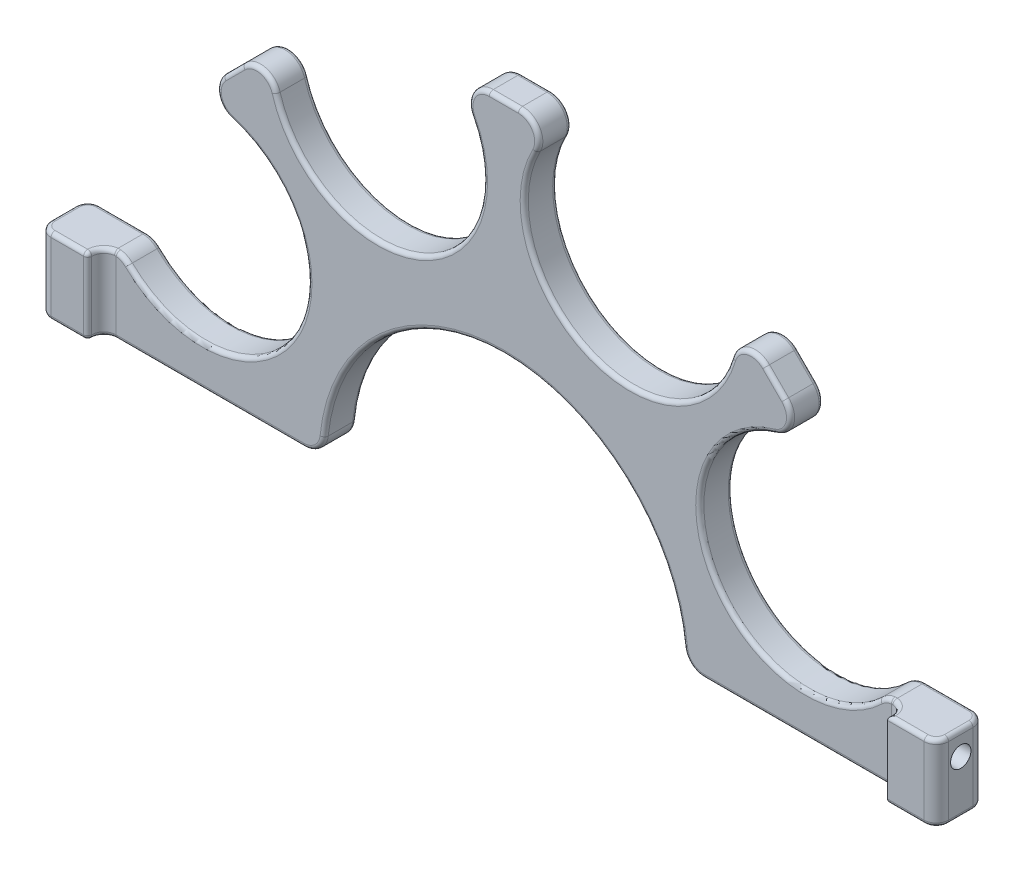
SolidWorks part; units mm, degrees
ref_plane "Front Plane" through (0, 0, 0) normal (0, 0, 1) x (1, 0, 0)
ref_plane "Top Plane" through (0, 0, 0) normal (0, 1, 0) x (1, 0, 0)
ref_plane "Right Plane" through (0, 0, 0) normal (1, 0, 0) x (0, 0, -1)
sketch "Sketch2" plane through (0, 0, 0) normal (0, 0, 1) x (1, 0, 0)
  line L0 (-74.1335, -21.5668) -> (-31, 21.5668) construction
  line L1 (-110.25, -57.5) -> (110.25, -57.5) construction
  line L2 (-110.25, -57.5) -> (-110.25, 57.5) construction
  line L3 (-110.25, 57.5) -> (110.25, 57.5) construction
  line L4 (110.25, -57.5) -> (110.25, 57.5) construction
  line L5 (-110.25, -57.5) -> (110.25, 57.5) construction
  line L6 (-110.25, 57.5) -> (110.25, -57.5) construction
  line L7 (-31, 21.5668) -> (31, 21.5668) construction
  line L8 (31, 21.5668) -> (74.1335, -21.5668) construction
  line L9 (0, 21.5668) -> (0, -21.5668) construction
  circle A0 centre (-74.1335, -21.5668) radius 27
  circle A1 centre (-31, 21.5668) radius 27
  circle A2 centre (31, 21.5668) radius 27
  circle A3 centre (74.1335, -21.5668) radius 27
  point P0 (0, 0)
  point P14 (0, 21.5668)
  point P24 (0, 0)
  dimension "D1" = 54
  dimension "D2" = 8
  dimension "D3" = 7
  dimension "D4" = 115
  dimension "D5" = 220.5
  dimension "D7" = 135
sketch "Sketch3" plane through (0, 0, 0) normal (0, 0, 1) x (1, 0, 0)
  line L0 (-13.7572, 41.0266) -> (13.7572, 41.0266)
  line L1 (-76.3601, 4.3377) -> (-56.9045, 23.7933)
  line L2 (76.3601, 4.3377) -> (56.9045, 23.7933)
  line L3 (31, 21.5668) -> (74.1335, -21.5668) construction
  line L4 (-74.1335, -21.5668) -> (-31, 21.5668) construction
  line L5 (-55.1453, 11.923) -> (-6.8547, 31.2105) construction
  line L6 (-55.1453, 11.923) -> (-56.9045, 23.7933) construction
  line L7 (-6.8547, 31.2105) -> (-13.7572, 41.0266) construction
  line L8 (-93.5934, -38.8096) -> (-110.25, -38.8096)
  line L9 (-110.25, -57.5) -> (-110.25, 57.5) construction
  line L10 (-110.25, -38.8096) -> (-110.25, -57.5)
  line L11 (-110.25, -57.5) -> (-44.3831, -57.5)
  line L12 (110.25, -57.5) -> (110.25, -38.8096)
  line L13 (110.25, -57.5) -> (110.25, 57.5) construction
  line L14 (110.25, -38.8096) -> (93.5934, -38.8096)
  line L15 (-64.4897, 2.5786) -> (-83.7773, -45.7121) construction
  line L16 (-64.4897, 2.5786) -> (-76.3601, 4.3377) construction
  line L17 (-83.7773, -45.7121) -> (-93.5934, -38.8096) construction
  line L18 (-110.25, -57.5) -> (110.25, -57.5) construction
  line L19 (-44.3831, -57.5) -> (44.3831, -57.5) construction
  line L20 (44.3831, -57.5) -> (110.25, -57.5)
  arc A0 (-93.5934, -38.8096) -> (-76.3601, 4.3377) centre (-74.1335, -21.5668) ccw
  arc A1 (-56.9045, 23.7933) -> (-13.7572, 41.0266) centre (-31, 21.5668) ccw
  arc A3 (13.7572, 41.0266) -> (56.9045, 23.7933) centre (31, 21.5668) ccw
  arc A4 (76.3601, 4.3377) -> (93.5934, -38.8096) centre (74.1335, -21.5668) ccw
  circle A5 centre (-31, 21.5668) radius 27 construction
  arc A6 (-76.3601, 4.3377) -> (-93.5934, -38.8096) centre (-74.1335, -21.5668) ccw construction
  arc A7 (-13.7572, 41.0266) -> (-56.9045, 23.7933) centre (-31, 21.5668) ccw construction
  arc A8 (56.9045, 23.7933) -> (13.7572, 41.0266) centre (31, 21.5668) ccw construction
  arc A9 (93.5934, -38.8096) -> (76.3601, 4.3377) centre (74.1335, -21.5668) ccw construction
  arc A10 (-44.3831, -57.5) -> (44.3831, -57.5) centre (0, -57.5) cw
  point P11 (0, -13.1169)
  dimension "D1" = 1
  dimension "D2" = 12
  dimension "D3" = 12
extrude "Boss-Extrude1" add sketch "Sketch3" along normal mid plane 8
sketch "Sketch4" plane through (0, 0, 4) normal (0, 0, 1) x (1, 0, 0)
  line L0 (-110.25, -57.5) -> (-44.3831, -57.5) construction
  line L1 (-110.25, -38.8096) -> (-98.25, -38.8096)
  line L2 (-110.25, -38.8096) -> (-110.25, -57.5)
  line L3 (-110.25, -57.5) -> (-98.25, -57.5)
  line L4 (-98.25, -38.8096) -> (-98.25, -57.5)
  dimension "D1" = 12
extrude "Boss-Extrude2" add sketch "Sketch4" along normal blind 4
sketch "Sketch5" plane through (0, -57.5, 0) normal (0, -1, 0) x (-1, 0, 0)
  line L0 (98.25, -8) -> (110.25, 4) construction
  circle A0 centre (104.25, -2) radius 2.5
  dimension "D1" = 5
extrude "Cut-Extrude1" cut sketch "Sketch5" against normal blind 8
sketch "Sketch6" plane through (-110.25, 0, 0) normal (-1, 0, 0) x (0, 0, 1)
  line L0 (8, -38.8096) -> (-4, -38.8096) construction
  line L1 (8, -57.5) -> (-4, -57.5) construction
  circle A0 centre (2, -44.5) radius 2.5
  point P4 (2, -38.8096)
  dimension "D1" = 5
  dimension "D2" = 13
extrude "Cut-Extrude2" cut sketch "Sketch6" against normal blind 10
mirror "Mirror1" about plane through (0, 0, 0) normal (1, 0, 0) of "Cut-Extrude2", "Cut-Extrude1", "Boss-Extrude2"
fillet "Fillet2" radius 5 10 edges at (44.3831, -57.5, 0) (93.5934, -38.8096, 0) (76.3601, 4.3377, 0) (56.9045, 23.7933, 0) (13.7572, 41.0266, 0) (-13.7572, 41.0266, 0) (-76.3601, 4.3377, 0) (-93.5934, -38.8096, 0) (-44.3831, -57.5, 0) (-56.9045, 23.7933, 0)
fillet "Fillet3" radius 3 6 edges at (-110.25, -48.1548, -4) (-110.25, -48.1548, 8) (110.25, -48.1548, 8) (110.25, -48.1548, -4) (98.25, -48.1548, 4) (-98.25, -48.1548, 4)
fillet "Fillet4" radius 1 67 edges at (-102.75, -57.5, 8) (102.75, -57.5, 8) (109.3713, -57.5, 7.1213) (110.25, -57.5, 2) (109.3713, -57.5, -3.1213) (78.1897, -57.5, -4) (45.7776, -56.2102, -4) (0, -13.1169, -4) (-45.7776, -56.2102, -4) (-78.1897, -57.5, -4) (-109.3713, -57.5, -3.1213) (-110.25, -57.5, 2) (98.25, -57.5, 7.5) (97.3713, -57.5, 4.8787) (72.1897, -57.5, 4) (45.7776, -56.2102, 4) (0, -13.1169, 4) (-45.7776, -56.2102, 4) (-72.1897, -57.5, 4) (98.25, -38.8096, 7.5) (97.5336, -38.8096, 5.0544) (93.6285, -39.271, 4) (51.667, -34.6533, 4) (70.2819, 6.9491, 4) (66.6323, 14.0655, 4) (59.5158, 17.7152, 4) (21.2405, -2.532, 4) (7.8604, 38.6091, 4) (0, 41.0266, 4) (-7.8604, 38.6091, 4) (-21.2405, -2.532, 4) (-59.5158, 17.7152, 4) (-66.6323, 14.0655, 4) (-70.2819, 6.9491, 4) (-51.667, -34.6533, 4) (-93.6285, -39.271, 4) (102.75, -38.8096, 8) (109.3713, -38.8096, 7.1213) (110.25, -38.8096, 2) (109.3713, -38.8096, -3.1213) (101.4883, -38.8096, -4) (93.8474, -39.1761, -4) (51.667, -34.6533, -4) (70.2819, 6.9491, -4) (66.6323, 14.0655, -4) (59.5158, 17.7152, -4) (21.2405, -2.532, -4) (7.8604, 38.6091, -4) (0, 41.0266, -4) (-7.8604, 38.6091, -4) (-21.2405, -2.532, -4) (-59.5158, 17.7152, -4) (-66.6323, 14.0655, -4) (-70.2819, 6.9491, -4) (-51.667, -34.6533, -4) (-93.8474, -39.1761, -4) (-101.4883, -38.8096, -4) (-109.3713, -38.8096, -3.1213) (-110.25, -38.8096, 2) (-109.3713, -38.8096, 7.1213) (-109.3713, -57.5, 7.1213) (-97.3713, -57.5, 4.8787) (-97.5336, -38.8096, 5.0544) (-102.75, -38.8096, 8) (-98.25, -48.1548, 8)
